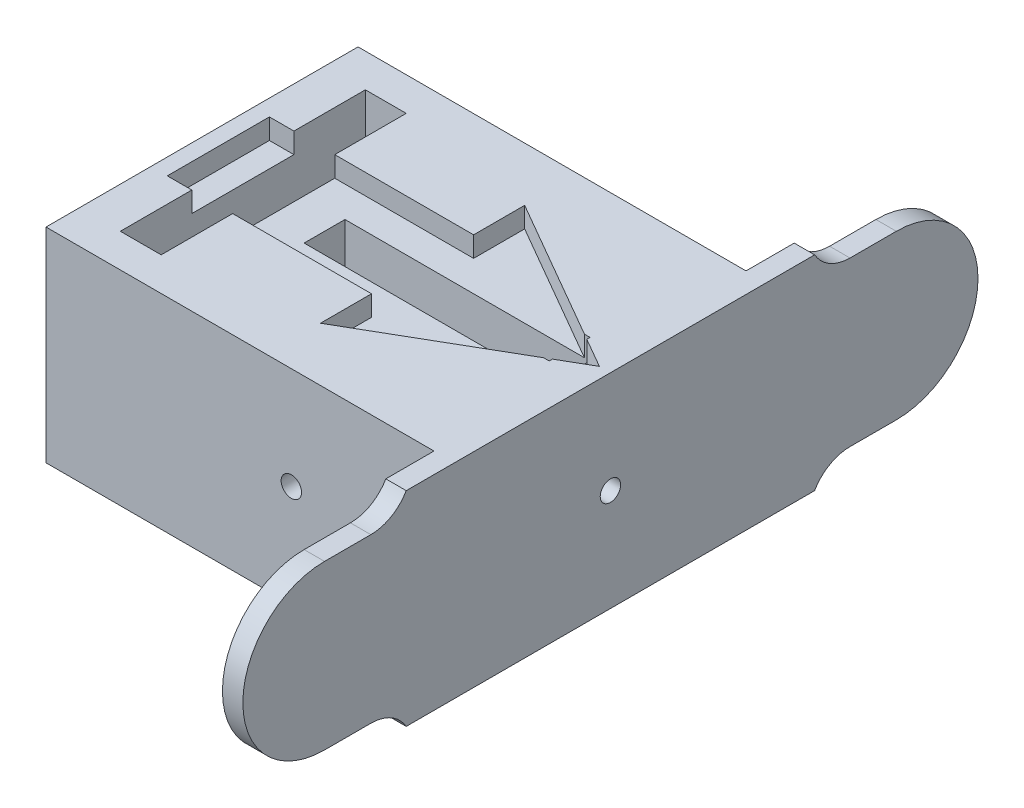
SolidWorks part; units mm, degrees
ref_plane "Front Plane" through (0, 0, 0) normal (0, 0, 1) x (1, 0, 0)
ref_plane "Top Plane" through (0, 0, 0) normal (0, 1, 0) x (1, 0, 0)
ref_plane "Right Plane" through (0, 0, 0) normal (1, 0, 0) x (0, 0, -1)
sketch "Sketch1" plane through (0, 0, 0) normal (0, 1, 0) x (1, 0, 0)
  line L1 (100, -100) -> (-100, -100)
  line L2 (100, -100) -> (100, 100)
  line L3 (100, 100) -> (-100, 100)
  line L4 (-100, -100) -> (-100, 100)
  line L5 (100, -100) -> (-100, 100) construction
  line L6 (100, 100) -> (-100, -100) construction
  point P0 (0, 0)
  dimension "D1" = 200
  dimension "D2" = 200
extrude "Boss-Extrude2" add sketch "Sketch1" along normal blind 100
sketch "Sketch2" plane through (100, 0, 0) normal (-1, 0, 0) x (0, 0, 1)
  line L2 (0, -1000.4254) -> (0, 48999.5746) construction
  line L3 (-1100, 50) -> (48900, 50) construction
  line L4 (-100, 100) -> (-100, 0) construction
  line L6 (140, 10) -> (-140, 10)
  line L8 (140, 90) -> (-140, 90)
  line L10 (140, 10) -> (-140, 90) construction
  line L11 (140, 90) -> (-140, 10) construction
  arc A0 (140, 10) -> (140, 90) centre (140, 50) ccw
  arc A1 (-140, 90) -> (-140, 10) centre (-140, 50) ccw
  point P6 (0, 50)
  point P16 (-100, 50)
  dimension "D1" = 80
  dimension "D2" = 140
extrude "Boss-Extrude3" add sketch "Sketch2" along normal blind 10
sketch "Sketch3" plane through (0, 100, 0) normal (0, 1, 0) x (1, 0, 0)
  line L0 (8, 25) -> (8, 50)
  line L1 (8, -25) -> (-92, -25) construction
  line L2 (8, -25) -> (8, 25) construction
  line L3 (8, 25) -> (-92, 25) construction
  line L4 (-92, -25) -> (-92, 25) construction
  line L5 (8, -25) -> (-92, 25) construction
  line L6 (8, 25) -> (-92, -25) construction
  line L7 (8, 50) -> (94.6025, 0)
  line L8 (94.6025, 0) -> (8, -50)
  line L9 (8, -50) -> (8, -25)
  line L10 (8, -25) -> (-92, -25)
  line L11 (-92, -25) -> (-92, 25)
  line L12 (-92, 25) -> (8, 25)
  line L13 (-100, 100) -> (-100, -100) construction
  point P0 (-42, 0)
  dimension "D1" = 50
  dimension "D2" = 100
  dimension "D3" = 100
  dimension "D4" = 60
  dimension "D5" = 8
extrude "Cut-Extrude1" cut sketch "Sketch3" against normal blind 10
sketch "Sketch4" plane through (0, 100, 0) normal (0, 1, 0) x (1, 0, 0)
  line L0 (-100, 100) -> (-100, -100) construction
  line L1 (80, -10) -> (-40, -10)
  line L2 (80, -10) -> (80, 10)
  line L3 (80, 10) -> (-40, 10)
  line L4 (-40, -10) -> (-40, 10)
  line L5 (80, -10) -> (-40, 10) construction
  line L6 (80, 10) -> (-40, -10) construction
  line L7 (100, -100) -> (100, 100) construction
  line L8 (-80, -60) -> (-60, -60)
  line L9 (-80, -60) -> (-80, 60)
  line L10 (-80, 60) -> (-60, 60)
  line L11 (-60, -60) -> (-60, 60)
  line L12 (-80, -60) -> (-60, 60) construction
  line L13 (-80, 60) -> (-60, -60) construction
  point P0 (20, 0)
  point P6 (-70, 0)
  dimension "D1" = 120
  dimension "D2" = 20
  dimension "D3" = 120
  dimension "D4" = 20
  dimension "D5" = 20
  dimension "D6" = 20
extrude "Cut-Extrude2" cut sketch "Sketch4" against normal through all
ref_point "Point2"
sketch "Sketch5" plane through (0, 0, 100) normal (0, 0, 1) x (1, 0, 0)
  line L0 (-100, 100) -> (-100, 0) construction
  circle A0 centre (20.1472, 50) radius 5
  point P2 (-100, 50)
  dimension "D1" = 10
extrude "Cut-Extrude3" cut sketch "Sketch5" against normal through all
sketch "Sketch6" plane through (-100, 0, 0) normal (-1, 0, 0) x (0, 0, 1)
  line L1 (-100, 100) -> (-100, 0) construction
  circle A0 centre (0, 50) radius 5
  point P5 (-100, 50)
  dimension "D1" = 10
extrude "Cut-Extrude4" cut sketch "Sketch6" against normal through all
ref_plane "Plane1" through (-70, 0, 0) normal (-1, 0, 0) x (0, 0, 1)
sketch "Sketch7" plane through (90, 0, 0) normal (-1, 0, 0) x (0, 0, 1)
  line L2 (0, -1000) -> (0, 49000) construction
  line L3 (-76.4025, 0) -> (-180, 0)
  line L4 (-76.4025, 0) -> (-76.4025, 100)
  line L5 (-76.4025, 100) -> (-180, 100)
  line L6 (-180, 0) -> (-180, 100)
  line L7 (-76.4025, 0) -> (-180, 100) construction
  line L8 (-76.4025, 100) -> (-180, 0) construction
  line L9 (180, 0) -> (76.4025, 0)
  line L10 (180, 0) -> (180, 100)
  line L11 (180, 100) -> (76.4025, 100)
  line L12 (76.4025, 0) -> (76.4025, 100)
  line L13 (180, 0) -> (76.4025, 100) construction
  line L14 (180, 100) -> (76.4025, 0) construction
  line L15 (-100, 100) -> (100, 100) construction
  line L16 (-100, 0) -> (100, 0) construction
  circle A7 centre (-140, 50) radius 40 construction
  point P0 (-128.2013, 50)
  point P2 (128.2013, 50)
  point P11 (0, 0)
  point P13 (0, 0)
  point P15 (0, 0)
  point P16 (-85.5642, 100)
  point P19 (-77.361, 0)
extrude "Cut-Extrude7" cut sketch "Sketch7" along normal through all
fillet "Fillet1" radius 20 4 edges at (95, 10, -100) (95, 90, -100) (95, 10, 100) (95, 90, 100)
